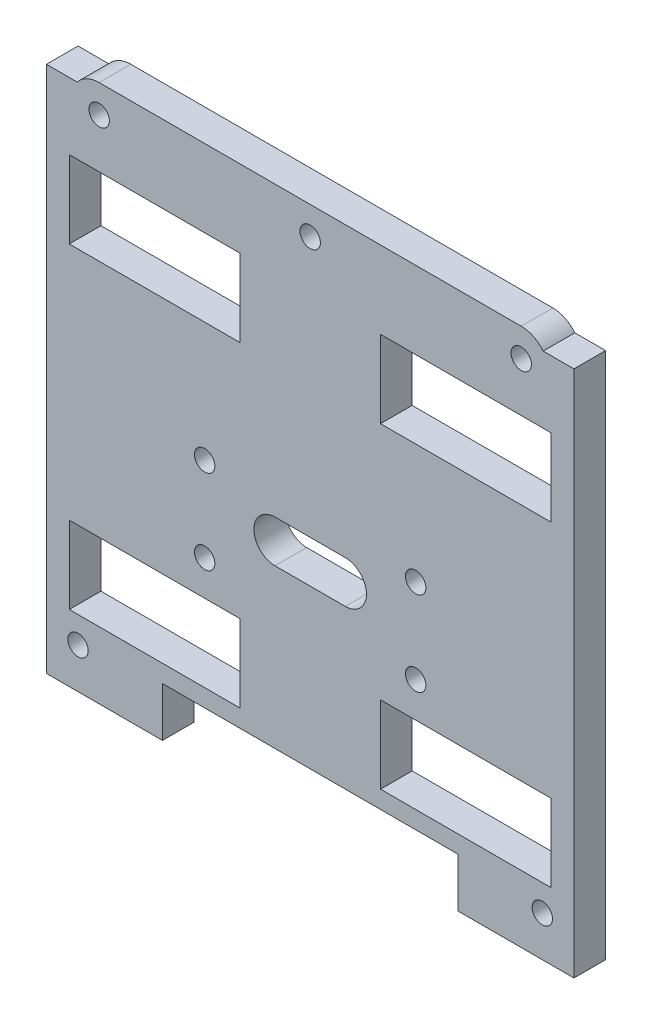
SolidWorks part; units mm, degrees
ref_plane "Front Plane" through (0, 0, 0) normal (0, 0, 1) x (1, 0, 0)
ref_plane "Top Plane" through (0, 0, 0) normal (0, 1, 0) x (1, 0, 0)
ref_plane "Right Plane" through (0, 0, 0) normal (1, 0, 0) x (0, 0, -1)
sketch "Sketch1" plane through (0, 0, 0) normal (0, 0, 1) x (1, 0, 0)
  line L0 (0, -37.5) -> (0, 37.5) construction
  line L1 (-47.5, -37.5) -> (47.5, -37.5)
  line L2 (-47.5, -37.5) -> (-47.5, 37.5)
  line L3 (-47.5, 37.5) -> (47.5, 37.5)
  line L4 (47.5, -37.5) -> (47.5, 37.5)
  line L5 (-47.5, -37.5) -> (47.5, 37.5) construction
  line L6 (-47.5, 37.5) -> (47.5, -37.5) construction
  line L7 (-47.5, 0) -> (47.5, 0) construction
  line L8 (-47.5, 22.5) -> (47.5, 22.5) construction
  line L9 (34.25, 17) -> (10, 28) construction
  line L10 (-34.25, 28) -> (-10, 28)
  line L11 (-34.25, 28) -> (-34.25, 17)
  line L12 (-34.25, 17) -> (-10, 17)
  line L13 (-10, 28) -> (-10, 17)
  line L14 (-34.25, 28) -> (-10, 17) construction
  line L15 (-34.25, 17) -> (-10, 28) construction
  line L16 (34.25, 28) -> (10, 17) construction
  line L17 (10, 28) -> (10, 17)
  line L18 (34.25, 17) -> (10, 17)
  line L19 (34.25, 28) -> (34.25, 17)
  line L20 (34.25, 28) -> (10, 28)
  line L21 (34.25, -28) -> (10, -17) construction
  line L22 (-34.25, -17) -> (-10, -28) construction
  line L23 (-34.25, -28) -> (-10, -17) construction
  line L24 (34.25, -17) -> (10, -28) construction
  line L25 (34.25, -28) -> (10, -28)
  line L26 (34.25, -28) -> (34.25, -17)
  line L27 (34.25, -17) -> (10, -17)
  line L28 (10, -28) -> (10, -17)
  line L29 (-10, -28) -> (-10, -17)
  line L30 (-34.25, -17) -> (-10, -17)
  line L31 (-34.25, -28) -> (-34.25, -17)
  line L32 (-34.25, -28) -> (-10, -28)
  point P0 (0, 0)
  point P12 (-22.125, 22.5)
  point P21 (22.125, 22.5)
  point P30 (22.125, -22.5)
  point P31 (-22.125, -22.5)
  dimension "D1" = 95
  dimension "D2" = 75
  dimension "D3" = 22.5
  dimension "D4" = 24.25
  dimension "D5" = 11
  dimension "D6" = 10
extrude "Boss-Extrude1" add sketch "Sketch1" along normal blind 4.5
sketch "Sketch8" plane through (0, 0, 4.5) normal (0, 0, 1) x (1, 0, 0)
  line L0 (-47.5, 37.5) -> (-47.5, -37.5) construction
  line L1 (47.5, -37.5) -> (47.5, 37.5) construction
  circle A0 centre (-47.5, 29.5) radius 8
  circle A1 centre (47.5, 29.5) radius 8
  dimension "D1" = 16
extrude "Boss-Extrude2" [suppressed] add sketch "Sketch8" against normal through all
sketch "Sketch2" plane through (0, 0, 4.5) normal (0, 0, 1) x (1, 0, 0)
  line L0 (0, -37.5) -> (0, 37.5) construction
  line L1 (-47.5, -37.5) -> (47.5, -37.5) construction
  line L2 (47.5, 37.5) -> (-47.5, 37.5) construction
  line L3 (-47.5, 0) -> (47.5, 0) construction
  line L4 (-47.5, 37.5) -> (-47.5, -37.5) construction
  line L5 (47.5, -37.5) -> (47.5, 37.5) construction
  line L6 (-40, 0) -> (40, 0) construction
  line L7 (-30, 35) -> (30, 35) construction
  circle A0 centre (-30, 35) radius 1.45
  circle A1 centre (30, 35) radius 1.45
  circle A2 centre (40, 0) radius 1.45
  circle A3 centre (-40, 0) radius 1.45
  circle A4 centre (0, 35) radius 1.45
  dimension "D1" = 2.9
  dimension "D7" = 2.9
  dimension "D8" = 2.9
  dimension "D9" = 2.9
  dimension "D2" = 30
  dimension "D3" = 35
  dimension "D4" = 80
  dimension "D5" = 40
  dimension "D6" = 0
extrude "screwHoles" cut sketch "Sketch2" against normal through all
sketch "Sketch3" plane through (0, 0, 4.5) normal (0, 0, 1) x (1, 0, 0)
  line L0 (-47.5, -20) -> (26.0486, -20) construction
  line L1 (-47.5, 37.5) -> (-47.5, -37.5) construction
  line L3 (0, 37.5) -> (0, -37.5) construction
  line L4 (47.5, 37.5) -> (-47.5, 37.5) construction
  line L5 (-47.5, -37.5) -> (47.5, -37.5) construction
  line L6 (18.95, -22.2) -> (9.05, -17.8) construction
  line L7 (-18.95, -17.8) -> (-9.05, -17.8)
  line L8 (-18.95, -17.8) -> (-18.95, -22.2)
  line L9 (-18.95, -22.2) -> (-9.05, -22.2)
  line L10 (-9.05, -17.8) -> (-9.05, -22.2)
  line L11 (-18.95, -17.8) -> (-9.05, -22.2) construction
  line L12 (-18.95, -22.2) -> (-9.05, -17.8) construction
  line L13 (18.95, -17.8) -> (9.05, -22.2) construction
  line L14 (9.05, -17.8) -> (9.05, -22.2)
  line L15 (18.95, -22.2) -> (9.05, -22.2)
  line L16 (18.95, -17.8) -> (18.95, -22.2)
  line L17 (18.95, -17.8) -> (9.05, -17.8)
  line L18 (-47.5, 37.5) -> (-47.5, -37.5) construction
  point P2 (-47.5, 0)
  point P12 (-14, -20)
  point P21 (14, -20)
  dimension "D1" = 9.9
  dimension "D3" = 14
  dimension "D4" = 20
extrude "BeltClamp" [suppressed] cut sketch "Sketch3" against normal through all
sketch "Sketch4" plane through (0, 0, 4.5) normal (0, 0, 1) x (1, 0, 0)
  line L0 (-47.5, 0) -> (47.5, 0) construction
  line L1 (-47.5, 37.5) -> (-47.5, -37.5) construction
  line L2 (47.5, -37.5) -> (47.5, 37.5) construction
  line L3 (0, 0) -> (0, 33.55) construction
  line L4 (-29.85, 2.175) -> (-20.15, 2.175)
  line L5 (-29.85, 2.175) -> (-29.85, -2.175)
  line L6 (-29.85, -2.175) -> (-20.15, -2.175)
  line L7 (-20.15, 2.175) -> (-20.15, -2.175)
  line L8 (-29.85, 2.175) -> (-20.15, -2.175) construction
  line L9 (-29.85, -2.175) -> (-20.15, 2.175) construction
  line L10 (29.85, -2.175) -> (20.15, 2.175) construction
  line L11 (29.85, 2.175) -> (20.15, -2.175) construction
  line L12 (20.15, 2.175) -> (20.15, -2.175)
  line L13 (29.85, -2.175) -> (20.15, -2.175)
  line L14 (29.85, 2.175) -> (29.85, -2.175)
  line L15 (29.85, 2.175) -> (20.15, 2.175)
  line L16 (-29.85, -2.175) -> (-20.15, 2.175) construction
  circle A0 centre (-40, 0) radius 1.45 construction
  circle A1 centre (0, 35) radius 1.45 construction
  point P6 (-25, 0)
  point P22 (25, 0)
  dimension "D3" = 0
  dimension "D2" = 4.35
  dimension "D4" = 25
extrude "Cut-Extrude3" [suppressed] cut sketch "Sketch4" against normal through all
sketch "Sketch5" plane through (0, 0, 4.5) normal (0, 0, 1) x (1, 0, 0)
  line L0 (-47.5, -9.75) -> (47.5, -9.75) construction
  line L1 (-47.5, 37.5) -> (-47.5, -37.5) construction
  line L2 (47.5, -37.5) -> (47.5, 37.5) construction
  line L4 (0, -37.5) -> (0, 37.5) construction
  line L5 (-47.5, -37.5) -> (47.5, -37.5) construction
  line L6 (47.5, 37.5) -> (-47.5, 37.5) construction
  line L7 (-30.825, -14.6) -> (-35.175, -4.9) construction
  line L8 (30.825, -4.9) -> (35.175, -4.9)
  line L9 (30.825, -4.9) -> (30.825, -14.6)
  line L10 (30.825, -14.6) -> (35.175, -14.6)
  line L11 (35.175, -4.9) -> (35.175, -14.6)
  line L12 (30.825, -4.9) -> (35.175, -14.6) construction
  line L13 (30.825, -14.6) -> (35.175, -4.9) construction
  line L14 (-30.825, -4.9) -> (-35.175, -14.6) construction
  line L15 (-35.175, -4.9) -> (-35.175, -14.6)
  line L16 (-30.825, -14.6) -> (-35.175, -14.6)
  line L17 (-30.825, -4.9) -> (-30.825, -14.6)
  line L18 (-30.825, -4.9) -> (-35.175, -4.9)
  line L19 (33, -9.75) -> (33, -37.5) construction
  line L20 (-33, -9.75) -> (-33, -37.5) construction
  line L21 (-33, -31.75) -> (33, -31.75) construction
  circle A0 centre (33, -31.75) radius 1.45
  circle A1 centre (-33, -31.75) radius 1.45
  point P15 (33, -9.75)
  point P24 (-33, -9.75)
  dimension "D5" = 2.9
  dimension "D2" = 9.7
  dimension "D3" = 4.35
  dimension "D4" = 33
  dimension "D6" = 22
  dimension "D1" = 9.75
extrude "Cut-Extrude4" [suppressed] cut sketch "Sketch5" against normal through all
sketch "Sketch9" plane through (0, 0, 4.5) normal (0, 0, 1) x (1, 0, 0)
  line L0 (47.5, 37.5) -> (-47.5, 37.5) construction
  line L1 (0, 37.5) -> (0, -37.5) construction
  line L2 (-47.5, -37.5) -> (47.5, -37.5) construction
  line L3 (50.5, 35) -> (45.5, 35) construction
  line L4 (-50.5, 35) -> (-45.5, 35) construction
  circle A0 centre (-30, 35) radius 4
  circle A1 centre (-30, 35) radius 1.45
  circle A2 centre (-30, 35) radius 1.45 construction
  circle A3 centre (30, 35) radius 1.45
  circle A4 centre (30, 35) radius 4
  point P17 (0, -37.5)
  dimension "D1" = 8
extrude "Boss-Extrude3" add sketch "Sketch9" against normal through all
sketch "Sketch10" plane through (0, 0, 4.5) normal (0, 0, 1) x (1, 0, 0)
  line L0 (-60, 37.5) -> (-37.5, 37.5)
  line L1 (-37.5, 37.5) -> (-37.5, -37.5)
  line L2 (-47.5, -37.5) -> (47.5, -37.5) construction
  line L3 (-37.5, -37.5) -> (-60, -37.5)
  line L4 (-60, -37.5) -> (-60, 37.5)
  line L5 (0, 37.5) -> (0, -37.5) construction
  line L6 (26.8775, 37.5) -> (-26.8775, 37.5) construction
  line L7 (60, -37.5) -> (60, 37.5)
  line L8 (37.5, -37.5) -> (60, -37.5)
  line L9 (37.5, 37.5) -> (37.5, -37.5)
  line L10 (60, 37.5) -> (37.5, 37.5)
  line L11 (-60, -37.5) -> (-60, 37.5)
  line L12 (-33.1225, 37.5) -> (-47.5, 37.5) construction
  line M3 (47.5, -37.5) -> (47.5, 37.5)
  line M7 (-47.5, 37.5) -> (-47.5, -37.5)
  line M8 (-47.5, -37.5) -> (47.5, -37.5)
  dimension "D3" = 0
  dimension "D1" = 75
  dimension "D2" = 60
extrude "Cut-Extrude5" cut sketch "Sketch10" against normal through all contours L1 L0 M7 M8 | L10 L9 M3 M8 region at (42.5, 0, 4.5) region at (-42.5, 0, 4.5)
sketch "Sketch11" plane through (0, 0, 4.5) normal (0, 0, 1) x (1, 0, 0)
  line L0 (-30, 39) -> (30, 39)
  line L1 (30, 39) -> (26.8775, 37.5)
  line L2 (26.8775, 37.5) -> (-26.8775, 37.5)
  line L3 (-26.8775, 37.5) -> (-30, 39)
  arc A0 (-26.8775, 37.5) -> (-33.1225, 37.5) centre (-30, 35) ccw construction
  arc A1 (33.1225, 37.5) -> (26.8775, 37.5) centre (30, 35) ccw construction
extrude "Boss-Extrude4" add sketch "Sketch11" against normal through all
sketch "Sketch12" plane through (0, 0, 4.5) normal (0, 0, 1) x (1, 0, 0)
  line L0 (-37.5, -12) -> (37.5, -12) construction
  line L1 (-37.5, 37.5) -> (-37.5, -37.5) construction
  line L2 (37.5, 37.5) -> (37.5, -37.5) construction
  line L3 (0, 0) -> (0, -37.5) construction
  line L4 (-37.5, -37.5) -> (37.5, -37.5) construction
  circle A0 centre (-15, -12) radius 1.45
  circle A1 centre (15, -12) radius 1.45
  dimension "D2" = 2.9
  dimension "D1" = 15
  dimension "D3" = 12
extrude "FanBraceScrews" cut sketch "Sketch12" against normal through all
sketch "Sketch13" plane through (0, 0, 4.5) normal (0, 0, 1) x (1, 0, 0)
  line L0 (-37.5, -37.5) -> (37.5, -37.5) construction
  line L1 (-21, -44.5) -> (21, -44.5)
  line L2 (-21, -44.5) -> (-21, -30.5)
  line L3 (-21, -30.5) -> (21, -30.5)
  line L4 (21, -44.5) -> (21, -30.5)
  line L5 (-21, -44.5) -> (21, -30.5) construction
  line L6 (-21, -30.5) -> (21, -44.5) construction
  point P0 (0, -37.5)
  dimension "D1" = 42
  dimension "D2" = 7
extrude "Cut-Extrude7" cut sketch "Sketch13" against normal through all
sketch "Sketch20" plane through (0, 0, 0) normal (0, 0, -1) x (-1, 0, 0)
  line L0 (15, -10.55) -> (15, 0) construction
  line L1 (0, 0) -> (0, 8.2059) construction
  line L2 (-15, -10.55) -> (-15, 0) construction
  circle A0 centre (15, -12) radius 1.45 construction
  circle A1 centre (15, 0) radius 1.45
  circle A2 centre (-15, 0) radius 1.45
  dimension "D1" = 12
extrude "Cut-Extrude11" cut sketch "Sketch20" against normal through all
sketch "Sketch14" plane through (0, 0, 4.5) normal (0, 0, 1) x (1, 0, 0)
  line L0 (15, -13.45) -> (15, 0) construction
  line L1 (0, 0) -> (0, -40.3958) construction
  line L2 (-15, -13.45) -> (-15, 0) construction
  circle A0 centre (15, -12) radius 1.45 construction
  circle A1 centre (15, 0) radius 1.45
  circle A2 centre (-15, 0) radius 1.45
  dimension "D2" = 2.9
  dimension "D1" = 12
extrude "Cut-Extrude8" [suppressed] cut sketch "Sketch14" against normal through all
sketch "Sketch15" plane through (0, 0, 4.5) normal (0, 0, 1) x (1, 0, 0)
  line L0 (-25, 1.5) -> (-25, -10.5) construction
  line L2 (0, 0) -> (0, -11.0705) construction
  line L3 (16, -8.3509) -> (25, -10.5) construction
  line L4 (25, 1.5) -> (25, -10.5) construction
  circle A0 centre (-25, 1.5) radius 1.45
  circle A1 centre (-25, -10.5) radius 1.45
  circle A2 centre (25, -10.5) radius 1.45
  circle A3 centre (25, 1.5) radius 1.45
  circle A5 centre (-15, -12) radius 1.45 construction
  dimension "D1" = 12
  dimension "D3" = 2.9
  dimension "D4" = 2.9
  dimension "D2" = 25
  dimension "D5" = 1.5
extrude "BeltClipScrews" [suppressed] cut sketch "Sketch15" against normal through all
sketch "Sketch16" [suppressed] plane through (0, 0, 4.5) normal (0, 0, 1) x (1, 0, 0)
  line L0 (0, 0) -> (0, -11.3016) construction
  line L1 (-29.85, 2.175) -> (-20.15, 2.175)
  line L2 (-29.85, 2.175) -> (-29.85, -2.175)
  line L3 (-29.85, -2.175) -> (-20.15, -2.175)
  line L4 (-20.15, 2.175) -> (-20.15, -2.175)
  line L5 (-35.175, -4.9) -> (-30.825, -4.9)
  line L6 (-35.175, -4.9) -> (-35.175, -14.6)
  line L7 (-35.175, -14.6) -> (-30.825, -14.6)
  line L8 (-30.825, -4.9) -> (-30.825, -14.6)
  line L9 (30.825, -4.9) -> (30.825, -14.6)
  line L10 (35.175, -14.6) -> (30.825, -14.6)
  line L11 (35.175, -4.9) -> (35.175, -14.6)
  line L12 (35.175, -4.9) -> (30.825, -4.9)
  line L13 (20.15, 2.175) -> (20.15, -2.175)
  line L14 (29.85, -2.175) -> (20.15, -2.175)
  line L15 (29.85, 2.175) -> (29.85, -2.175)
  line L16 (29.85, 2.175) -> (20.15, 2.175)
  line L17 (-30.825, -4.9) -> (-30.825, -14.6)
extrude "Boss-Extrude5" [suppressed] add sketch "Sketch16" against normal through all contours L8 L5 L6 L7 | L4 L1 L2 L3 | L15 L16 L13 L14 | L11 L12 L9 L10
sketch "Sketch17" [suppressed] plane through (0, 0, 4.5) normal (0, 0, 1) x (1, 0, 0)
  line L0 (0, -30.5) -> (0, 0) construction
  line L1 (21, -30.5) -> (-21, -30.5) construction
  line L2 (-37.5, -37.5) -> (-46.5, -37.5)
  line L3 (-46.5, -37.5) -> (-46.5, -22.5)
  line L4 (-46.5, -22.5) -> (-43.5, -22.5)
  line L5 (-43.5, -22.5) -> (-43.5, -32.5)
  line L6 (-43.5, -32.5) -> (-37.5, -32.5)
  line L7 (-37.5, 37.5) -> (-37.5, -37.5) construction
  line L8 (-37.5, -32.5) -> (-37.5, -37.5)
  line L9 (-37.5, -37.5) -> (-37.5303, -37.4889)
  dimension "D1" = 3
  dimension "D2" = 6
  dimension "D3" = 5
  dimension "D4" = 15
extrude "Boss-Extrude6" [suppressed] add sketch "Sketch17" against normal through all contours L8 L6 L5 L4 L3 L2
sketch "Sketch18" plane through (0, 0, 0) normal (0, 0, 1) x (1, 0, 0)
  line L0 (0, -30.5) -> (0, 0) construction
  line L1 (-37.5, -37.5) -> (-21, -37.5) construction
  line L7 (-37.5, -27.5) -> (-37.5, -22.5)
  line L9 (-43.5, -27.5) -> (-37.5, -27.5)
  line L10 (-37.5, -30) -> (-45.5, -30) construction
  line L11 (-37.5, 37.5) -> (-37.5, -37.5) construction
  line L12 (-43.5, -37.5) -> (-43.5, -27.5)
  line L13 (-46.5, -37.5) -> (-43.5, -37.5)
  line L14 (-46.5, -22.5) -> (-46.5, -37.5)
  line L15 (-37.5, -22.5) -> (-46.5, -22.5)
  dimension "D1" = 6
  dimension "D2" = 15
  dimension "D3" = 5
extrude "Boss-Extrude7" [suppressed] add sketch "Sketch18" along normal through all
mirror "Mirror1" [suppressed] about plane through (0, 0, 0) normal (1, 0, 0)
fillet "Fillet1" [suppressed] radius 2
mirror "Mirror2" [suppressed] about plane through (0, 0, 0) normal (1, 0, 0)
fillet "Fillet2" [suppressed] radius 2
sketch "Sketch19" plane through (0, 0, 4.5) normal (0, 0, 1) x (1, 0, 0)
  line L0 (-5, -5) -> (5, -5) construction
  line L1 (-5, -2) -> (5, -2)
  line L2 (-5, -8) -> (5, -8)
  line L3 (0, 0) -> (0, -15.8058) construction
  arc A0 (-5, -2) -> (-5, -8) centre (-5, -5) ccw
  arc A1 (5, -8) -> (5, -2) centre (5, -5) ccw
  point P2 (0, -5)
  dimension "D1" = 10
  dimension "D2" = 6
  dimension "D3" = 0
  dimension "D4" = 5
extrude "Cut-Extrude9" cut sketch "Sketch19" against normal through all
sketch "Sketch21" plane through (0, 0, 0) normal (0, 0, -1) x (-1, 0, 0)
  line L0 (0, 0) -> (0, -30.5) construction
  line L1 (-21, -30.5) -> (21, -30.5) construction
  circle A0 centre (-33, -31.75) radius 1.45
  circle A1 centre (33, -31.75) radius 1.45
  dimension "D1" = 2.9
  dimension "D2" = 33
  dimension "D3" = 31.75
extrude "Cut-Extrude12" cut sketch "Sketch21" against normal through all
equation "\"X-ROD-SPACING\"=45"
equation "\"Y-ROD-SPACING\"=75"
equation "\"Z-ROD-SPACING\"=17.5"
equation "\"Y-BED-OFFSET\"=2"
equation "\"Y-BED-ROD-INSET\"=3.5"
equation "\"Y-BED-SCREW-SPACING\"=209"
equation "\"Y-BED-SCREW-CUTOUT-SLOT-HEIGHT\"=2.5"
equation "\"T-SLOT-NUT-FILLET-RADIUS\"=0.5"
equation "\"T-SLOT-SCREW-SHAFT-RADIUS\"=1.55"
equation "\"T-SLOT-SCREW-SHAFT-CUTOUT-LENGTH\"=11"
equation "\"T-SLOT-NUT-DEPTH\"=3.5"
equation "\"T-SLOT-NUT-WIDTH\"=2.85"
equation "\"T-SLOT-NUT-END-DISTANCE\"=8"
equation "\"ACRYLIC-THICKNESS\"=10"
equation "\"ACRYLIC-THICKNESS2\"=4.5"
equation "\"ACRYLIC-TAB-CUTOUT-SIZE\"=\"ACRYLIC-THICKNESS\"+\"ACRYLIC-TAB-TOLERANCE\"*2"
equation "\"ACRYLIC-TAB-WIDTH\"=\"ACRYLIC-THICKNESS\""
equation "\"ACRYLIC-M3-HOLE\"=2.9"
equation "\"SMOOTHROD-CAP-SCREW-DISTANCE\"=20"
equation "\"FRAME-WIDTH-INNER\"=370"
equation "\"NEMA17-HOLE-SPACING\"=31"
equation "\"NEMA17-CENTRAL-CUTOUT\"=22.5"
equation "\"Z-BRACKET-REACH\"=57"
equation "\"Z-ROD-INSET\"=13.5"
equation "\"TOP-BRACKET-SPACING\"=40"
equation "\"SMOOTHROD-X-LENGTH\"=350"
equation "\"SMOOTHROD-Y-LENGTH\"=350"
equation "\"SMOOTHROD-Z-LENGTH\"=350"
equation "\"SMOOTHROD-TIGHTENING-HEADROOM\"=.25"
equation "\"LEADSCREW-Z-LENGTH\"=300"
equation "\"SCREW-LENGTH-FRAME\"=\"ACRYLIC-THICKNESS\" + 10"
equation "\"SCREW-LENGTH-MOTOR\"=\"ACRYLIC-THICKNESS\" + 5"
equation "\"SCREW-HEAD-RADIUS\"=6"
equation "\"PRINTED-X-SMOOTHROD-DIAMETER\"=8.8"
equation "\"PRINTED-X-SMOOTHROD-CUTOUT\"=10"
equation "\"PRINTED-X-BASE-HEIGHT\"=10"
equation "\"PRINTED-LM8UU-CUTOUT-SIZE\"=15.5"
equation "\"PRINTED-LM8UU-CUTOUT-LENGTH\"=24.5"
equation "\"PRINTED-X-IDLER-HEIGHT\"=16"
equation "\"PSU-MOUNTING-WIDTH\"=95"
equation "\"PSU-MOUNTING-HEIGHT\"=177"
equation "\"Y-BELT-TO-ROD-DISTANCE\"=20"
equation "\"SPOOL-HOLDER-ROD-SPACING\"=150"
equation "\"D3@Sketch1\"=\"X-ROD-SPACING\"/2"
equation "\"D4@Sketch1\"=\"ACRYLIC-X-CARRIAGE-LM8UU-CUTOUT-WIDTH\""
equation "\"D1@Boss-Extrude1\"=\"ACRYLIC-THICKNESS2\""
equation "\"D1@Sketch2\"=\"ACRYLIC-M3-HOLE\""
equation "\"D1@Sketch3\"=\"ACRYLIC-TAB-CUTOUT-SIZE\""
equation "\"D2@Sketch3\"=\"ACRYLIC-THICKNESS2\"+\"ACRYLIC-TAB-TOLERANCE\"*2"
equation "\"ACRYLIC-X-CARRIAGE-WIDTH\"=55"
equation "\"ACRYLIC-X-CARRIAGE-HEIGHT\"=75"
equation "\"D2@Sketch1\"=\"ACRYLIC-X-CARRIAGE-HEIGHT\""
equation "\"ACRYLIC-X-CARRIAGE-CENTER-TAB-SPACING\"=14"
equation "\"D3@Sketch3\"=\"ACRYLIC-X-CARRIAGE-CENTER-TAB-SPACING\""
equation "\"SCREW-LENGTH-EXTRUDER\"=28"
equation "\"ACRYLIC-X-CARRIAGE-SCREW-SPACING-X\"=15"
equation "\"ACRYLIC-X-CARRIAGE-SCREW-SPACING-Y\"=33"
equation "\"D1@Sketch4\"=\"ACRYLIC-TAB-WIDTH\"-\"KERF\"*4"
equation "\"D2@Sketch4\"=\"ACRYLIC-THICKNESS2\"-\"KERF\"*2"
equation "\"D2@Sketch5\"=\"ACRYLIC-TAB-WIDTH\"-\"KERF\"*4"
equation "\"D3@Sketch5\"=\"ACRYLIC-THICKNESS2\"-\"KERF\"*2"
equation "\"ACRYLIC-X-CARRIAGE-EXTRUDER-SHELF-DEPTH\"=\"ACRYLIC-X-CARRIAGE-EXTRUDER-OFFSET\" + 28"
equation "\"ACRYLIC-X-CARRIAGE-EXTRUDER-BRACE-SPACING\"=23"
equation "\"D4@Sketch5\"=\"ACRYLIC-X-CARRIAGE-DUAL-MOUNT-BRACE-WIDTH\""
equation "\"D1@Sketch5\"=\"ACRYLIC-THICKNESS2\"/2 + 7.5"
equation "\"D4@Sketch2\"=\"ACRYLIC-X-CARRIAGE-DUAL-MOUNT-SCREW-WIDTH\"*2"
equation "\"D5@Sketch2\"=\"ACRYLIC-X-CARRIAGE-DUAL-MOUNT-SCREW-WIDTH\""
equation "\"D7@Sketch2\"=\"ACRYLIC-M3-HOLE\""
equation "\"D8@Sketch2\"=\"ACRYLIC-M3-HOLE\""
equation "\"ACRYLIC-X-CARRIAGE-LM8UU-CUTOUT-WIDTH\"=24.25"
equation "\"ACRYLIC-TAB-TOLERANCE\"=-.05"
equation "\"ACRYLIC-X-CARRIAGE-EXTRUDER-OFFSET\"=26"
equation "\"ACRYLIC-X-CARRIAGE-EXTRUDER-ANGLE\"=90"
equation "\"ACRYLIC-X-CARRIAGE-EXTRUDER-BRACE-TAB-OFFSET\"=20"
equation "\"ACRYLIC-X-CARRIAGE-EXTRUDER-BRACE-HEIGHT\"=35"
equation "\"ACRYLIC-X-CARRIAGE-EXTRUDER-BRACE-SCREW-SPACING\"=22"
equation "\"D5@Sketch5\"=\"ACRYLIC-M3-HOLE\""
equation "\"ACRYLIC-X-CARRIAGE-DUAL-WIDTH-MULTIPLIER\"=1.65"
equation "\"ACRYLIC-X-CARRIAGE-DUAL-HOTEND-SPACING\"=42"
equation "\"ACRYLIC-X-CARRIAGE-DUAL-WIDTH\"=75"
equation "\"ACRYLIC-X-CARRIAGE-DUAL-HOTEND-SEPARATION\"=36"
equation "\"ACRYLIC-X-CARRIAGE-DUAL-MOUNT-PLATE-DEPTH\"=75"
equation "\"ACRYLIC-X-CARRIAGE-DUAL-MOUNT-BRACE-WIDTH\"=33"
equation "\"ACRYLIC-X-CARRIAGE-DUAL-MOUNT-SCREW-WIDTH\"=40"
equation "\"D9@Sketch2\"=\"ACRYLIC-M3-HOLE\""
equation "\"ACRYLIC-X-CARRIAGE-LM8UU-CUTOUT-HEIGHT\"=11.0"
equation "\"D5@Sketch1\"=\"ACRYLIC-X-CARRIAGE-LM8UU-CUTOUT-HEIGHT\""
equation "\"D1@Sketch10\"=\"ACRYLIC-X-CARRIAGE-DUAL-WIDTH\""
equation "\"D2@Sketch12\"=\"ACRYLIC-M3-HOLE\""
equation "\"D2@Sketch14\"=\"ACRYLIC-M3-HOLE\""
equation "\"D3@Sketch15\"=\"ACRYLIC-M3-HOLE\""
equation "\"D4@Sketch15\"=\"ACRYLIC-M3-HOLE\""
equation "\"KERF\"=0.075"
equation "\"ACRYLIC-THICKNESS-TAB-CUTOUT-WIDTH\"=\"ACRYLIC-THICKNESS\"-\"KERF\"*2"
equation "\"ACRYLIC-THICKNESS-TAB-CUTOUT-HEIGHT\"=\"ACRYLIC-TAB-WIDTH\"-\"KERF\"*4"
equation "\"ACRYLIC-THICKNESS2-TAB-CUTOUT-WIDTH\"=\"ACRYLIC-THICKNESS2\"-\"KERF\"*2"
equation "\"ACRYLIC-THICKNESS2-TAB-CUTOUT-HEIGHT\"=\"ACRYLIC-TAB-WIDTH\"-\"KERF\"*4"
equation "\"PRINTED-M3-HOLE\"=3.5"
equation "\"PRINTED-M3-NUT-AF\"=6.25"
equation "\"ACRYLIC-X-CARRIAGE-DUAL-FAN-OFFSET\"=52"
equation "\"ACRYLIC-X-CARRIAGE-DUAL-FAN-HEIGHT\"=20"
equation "\"BLOWER-FAN-WIDTH\"=15"
equation "\"D1@Sketch21\"=\"ACRYLIC-M3-HOLE\""
equation "\"D2@Sketch21\"=\"ACRYLIC-X-CARRIAGE-DUAL-MOUNT-BRACE-WIDTH\""
equation "\"D3@Sketch21\"=\"ACRYLIC-THICKNESS2\"/2 + 7.5+22"
